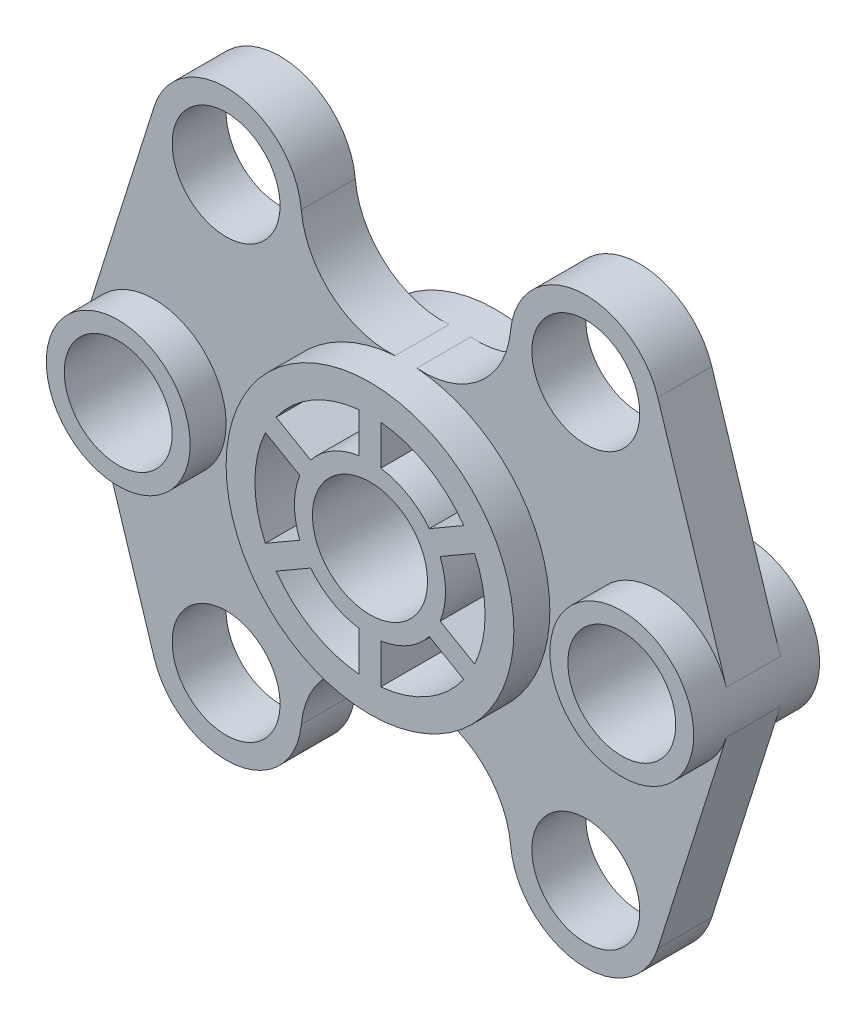
SolidWorks part; units mm, degrees
ref_plane "Front Plane" through (0, 0, 0) normal (0, 0, 1) x (1, 0, 0)
ref_plane "Top Plane" through (0, 0, 0) normal (0, 1, 0) x (1, 0, 0)
ref_plane "Right Plane" through (0, 0, 0) normal (1, 0, 0) x (0, 0, -1)
sketch "Sketch1" plane through (0, 0, 0) normal (0, 0, 1) x (1, 0, 0)
  line L0 (0, 0) -> (50000, 0) construction
  line L1 (0, -1080) -> (0, -40) construction
  line L2 (89.0713, -6.0238) -> (70.0249, -66.325)
  line L3 (89.0713, 6.0238) -> (70.0249, 66.325)
  line L4 (-89.0713, -6.0238) -> (-70.0249, -66.325)
  line L5 (-89.0713, 6.0238) -> (-70.0249, 66.325)
  line L6 (-29.0908, -13.3315) -> (-19.5, -7.7942)
  line L7 (-26.0908, -18.5276) -> (-16.5, -12.9904)
  line L8 (3, -31.8591) -> (3, -20.7846)
  line L9 (-3, -31.8591) -> (-3, -20.7846)
  line L10 (0, -32) -> (0, 50000) construction
  line L11 (-26.0908, 18.5276) -> (-16.5, 12.9904)
  line L12 (-29.0908, 13.3315) -> (-19.5, 7.7942)
  line L13 (3, 31.8591) -> (3, 20.7846)
  line L14 (-3, 31.8591) -> (-3, 20.7846)
  line L15 (29.0908, 13.3315) -> (19.5, 7.7942)
  line L16 (26.0908, 18.5276) -> (16.5, 12.9904)
  line L17 (26.0908, -18.5276) -> (16.5, -12.9904)
  line L18 (29.0908, -13.3315) -> (19.5, -7.7942)
  circle A0 centre (0, 0) radius 21
  circle A1 centre (0, 0) radius 32
  circle A2 centre (0, 0) radius 16
  circle A3 centre (0, 0) radius 40
  circle A4 centre (70, 0) radius 15
  circle A5 centre (70, 0) radius 20
  circle A6 centre (50, -60) radius 15
  arc A7 (29.0895, -61.9371) -> (70.0249, -66.325) centre (50, -60) ccw
  arc A8 (29.0895, -61.9371) -> (3, -39.8873) centre (4.8274, -64.1847) ccw
  arc A9 (29.0895, 61.9371) -> (3, 39.8873) centre (4.8274, 64.1847) cw
  arc A10 (29.0895, 61.9371) -> (70.0249, 66.325) centre (50, 60) cw
  circle A11 centre (50, 60) radius 15
  circle A12 centre (-50, 60) radius 15
  arc A13 (-29.0895, 61.9371) -> (-70.0249, 66.325) centre (-50, 60) ccw
  arc A14 (-29.0895, 61.9371) -> (-3, 39.8873) centre (-4.8274, 64.1847) ccw
  arc A15 (-29.0895, -61.9371) -> (-3, -39.8873) centre (-4.8274, -64.1847) cw
  arc A16 (-29.0895, -61.9371) -> (-70.0249, -66.325) centre (-50, -60) cw
  circle A17 centre (-50, -60) radius 15
  circle A18 centre (-70, 0) radius 20
  circle A19 centre (-70, 0) radius 15
  point P72 (0, 0)
  dimension "D1" = 42
  dimension "D2" = 64
  dimension "D3" = 32
  dimension "D4" = 80
  dimension "D5" = 30
  dimension "D6" = 40
  dimension "D7" = 30
  dimension "D8" = 42
  dimension "D12" = 6
  dimension "D9" = 50
  dimension "D10" = 20
  dimension "D11" = 60
  dimension "D14" = 6
  dimension "D13" = 6
extrude "Boss-Extrude1" [suppressed] add sketch "Sketch1" along normal blind 10 contours L5 A18 L4 A16 A15 A3 A14 A13 A17 A12 | A10 A9 A3 A8 A7 L2 A5 L3 A6 A11 | L12 A1 L6 A0 | L14 A1 L11 A0 | L16 A1 L13 A0 | L8 A1 L17 A0 | L7 A1 L9 A0 | L18 A1 L15 A0
extrude "Boss-Extrude2" add sketch "Sketch1<4>" along normal mid plane 35 contours A18 A19 | A5 A4 | L11 A1 L12 A0 | L6 A1 L7 A0 | L9 A1 L8 A0 | L17 A1 L18 A0 | L15 A1 L16 A0 | L13 A1 L14 A0 | A3 A1 | A0 A2 region at (50.5657, 0, 0) region at (0, -38.8686, 0) region at (-89.4343, 0, 0) region at (-22.8982, -13.2203, 0) region at (-20.406, 0, 0) region at (-22.8982, 13.2203, 0) region at (0, -26.4406, 0) region at (0, 26.4406, 0) region at (22.8982, -13.2203, 0) region at (22.8982, 13.2203, 0)
sketch "Sketch1<4>" plane through (0, 0, 0) normal (0, 0, 1) x (1, 0, 0) same geometry as "Sketch1"
extrude "Boss-Extrude3" add sketch "Sketch1<5>" along normal mid plane 15 contours L5 A18 L4 A16 A15 A3 A14 A13 A17 A12 | A10 A9 A3 A8 A7 L2 A5 L3 A6 A11 region at (77.7988, -35.6218, 0) region at (-21.7398, -44.1738, 0)
sketch "Sketch1<5>" plane through (0, 0, 0) normal (0, 0, 1) x (1, 0, 0) same geometry as "Sketch1"
